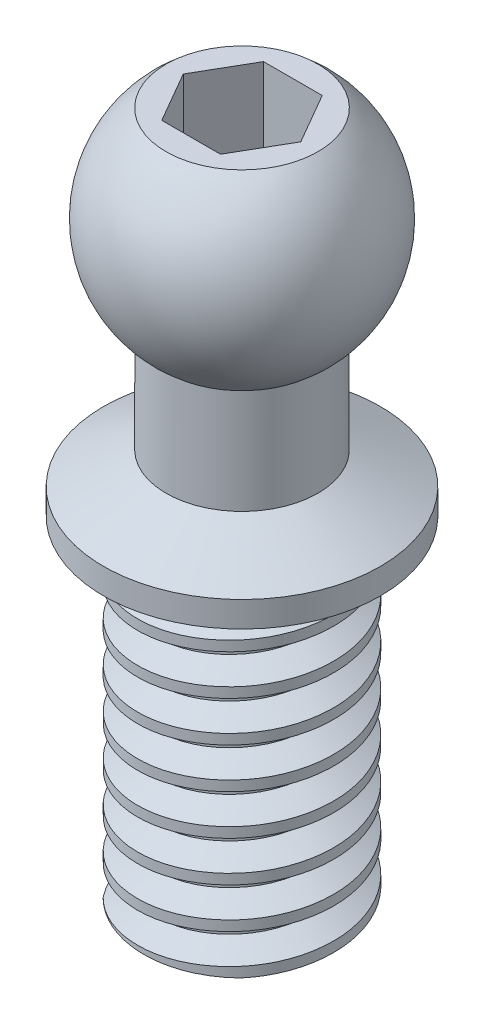
SolidWorks part; units mm, degrees
material "1060 Alloy"
ref_plane "Front Plane" through (0, 0, 0) normal (0, 0, 1) x (1, 0, 0)
ref_plane "Top Plane" through (0, 0, 0) normal (0, 1, 0) x (1, 0, 0)
ref_plane "Right Plane" through (0, 0, 0) normal (1, 0, 0) x (0, 0, -1)
sketch "Sketch1" plane through (0, 0, 0) normal (0, 1, 0) x (1, 0, 0)
  circle A0 centre (0, 0) radius 1.5
  dimension "D1" = 3
extrude "Boss-Extrude1" add sketch "Sketch1" along normal blind 6.5
thread "Thread1" pitch 0.7937 method extrude trim with end face yes profile "Thread Profile1" start angle 0, offset 0, length 0, pitch 0.7937, diameter 3
ref_plane "Plane1" through (-1.5, 6.5, 0) normal (0, 0, -1) x (1, 0, 0)
sketch "Thread Profile1" plane through (-1.5, 6.5, 0) normal (0, 0, -1) x (1, 0, 0)
  line L0 (0, 0) -> (0, 0.7937) construction
  line L11 (0, 0) -> (0, 0.6945)
  line L12 (0, 0.6945) -> (-0.4296, 0.4465)
  line L13 (-0.4296, 0.4465) -> (-0.4296, 0.248)
  line L15 (-0.4296, 0.248) -> (0, 0)
  line L17 (-0.4296, 0.3473) -> (0, 0.3473) construction
  point P2 (0, 0)
  dimension "Pitch" = 0.7937
  dimension "Profile_Angle" = 60
  dimension "Profile_Land" = 0.1984
  dimension "Profile_Height" = 0.4296
sketch "Sketch8" plane through (0, 0, 0) normal (0, 0, 1) x (1, 0, 0)
  line L0 (1.5, 6.5) -> (-1.5, 6.5) construction
  line L1 (1.5, 6.5) -> (-1.5, 6.5)
  line L2 (0, 6.5) -> (0, 13) construction
  line L3 (0, 6.5) -> (-2.722, 6.5)
  line L4 (-2.722, 6.5) -> (-2.722, 7.0032)
  line L5 (-2.722, 7.0032) -> (-1.4922, 7.6322)
  line L6 (-1.4922, 7.6322) -> (-1.4922, 9.687)
  line L7 (-1.4922, 13.4465) -> (0, 13.4465)
  line L8 (0, 13.4465) -> (0, 6.5)
  arc A0 (-1.4922, 9.687) -> (-1.4922, 13.4465) centre (0, 11.5668) cw
  dimension "D2" = 2.4
  dimension "D1" = 2.722
  dimension "D3" = 0.5032
  dimension "D4" = 27.09
  dimension "D5" = 1.2298
  dimension "D6" = 2.0548
  dimension "D7" = 6.5
revolve "Revolve1" add sketch "Sketch8" angle 360 about L2 region at (-1.0329, 10.0262, 0)
sketch "Sketch13" plane through (0, 13.4465, 0) normal (0, 1, 0) x (1, 0, 0)
  line L0 (0, 0) -> (0, 2.8918) construction
  line L1 (0.5774, 1) -> (-0.5774, 1)
  line L2 (-0.5774, 1) -> (-1.1547, 0)
  line L3 (-1.1547, 0) -> (-0.5774, -1)
  line L4 (-0.5774, -1) -> (0.5774, -1)
  line L5 (0.5774, -1) -> (1.1547, 0)
  line L6 (1.1547, 0) -> (0.5774, 1)
  circle A0 centre (0, 0) radius 1 construction
  dimension "D1" = 2
extrude "Cut-Extrude1" cut sketch "Sketch13" against normal blind 3
